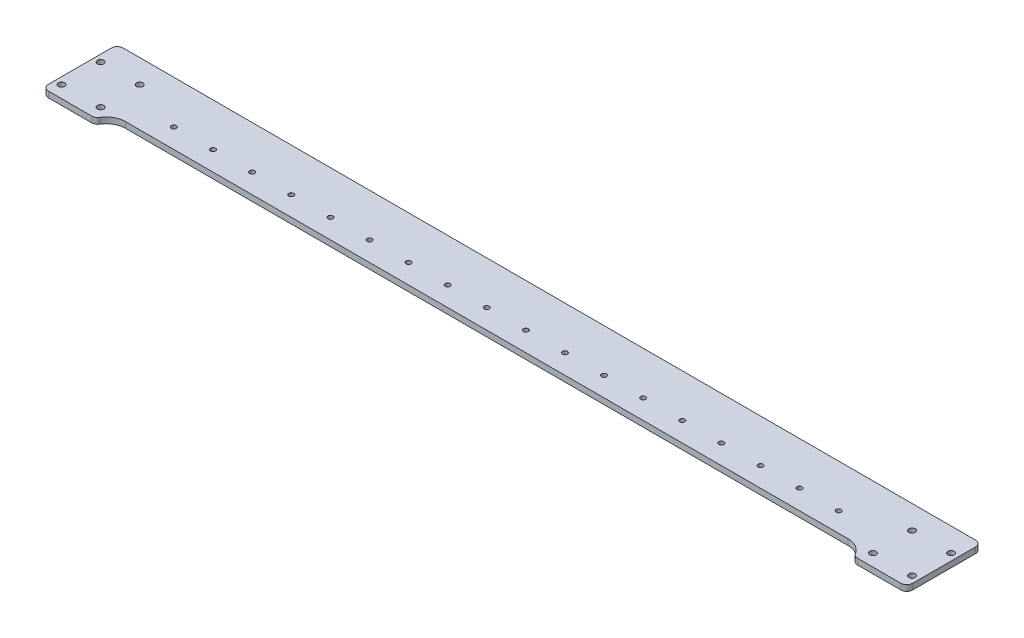
SolidWorks part; units mm, degrees
material "AISI 1045 Steel, cold drawn"
ref_plane "Front Plane" through (0, 0, 0) normal (0, 0, 1) x (1, 0, 0)
ref_plane "Top Plane" through (0, 0, 0) normal (0, 1, 0) x (1, 0, 0)
ref_plane "Right Plane" through (0, 0, 0) normal (1, 0, 0) x (0, 0, -1)
sketch "Sketch1" plane through (0, 0, 0) normal (0, 1, 0) x (1, 0, 0)
  line L0 (0, 0) -> (194, 0)
  line L1 (194, 0) -> (194, -6.2)
  line L2 (194, -6.2) -> (221, -6.2)
  line L3 (221, -6.2) -> (221, 26.2)
  line L4 (221, 26.2) -> (0, 26.2) construction
  line L7 (0, 0) -> (0, 26.2)
  line L8 (221, 10) -> (0, 10) construction
  line L9 (221, 26.2) -> (221, 32)
  line L10 (221, 32) -> (0, 32)
  line L11 (0, 32) -> (0, 26.2)
  dimension "D1" = 194
  dimension "D2" = 27
  dimension "D3" = 10
  dimension "D4" = 32.4
  dimension "D5" = 22
extrude "Boss-Extrude1" add sketch "Sketch1" along normal blind 3
hole_wizard "M3 Clearance Hole1" positions "Sketch2" profile "Sketch3" hole size "M3" standard "ANSI Metric" end condition through all
sketch "Sketch2" plane through (0, 3, 0) normal (0, 1, 0) x (1, 0, 0)
  line L1 (217.5, 0) -> (197.5, 0)
  line L2 (217.5, 0) -> (217.5, 20)
  line L3 (217.5, 20) -> (197.5, 20)
  line L4 (197.5, 0) -> (197.5, 20)
  line L5 (217.5, 0) -> (197.5, 20) construction
  line L6 (217.5, 20) -> (197.5, 0) construction
  line L10 (207.5, 10) -> (207.5, -6.2) construction
  line L13 (194, -6.2) -> (221, -6.2) construction
  line L17 (0, 0) -> (194, 0) construction
  point P2 (197.5, 20)
  point P35 (217.5, 0)
  point P36 (217.5, 20)
  point P37 (197.5, 0)
  dimension "D1" = 20
  dimension "D2" = 10
sketch "Sketch3" plane through (197.5, 3, -20) normal (1, 0, 0) x (0, 0, 1)
  line L0 (0, 0) -> (0, 3)
  line L1 (0, 3) -> (1.6, 3)
  line L2 (1.6, 3) -> (1.6, 0.025)
  line L3 (1.6, 0.025) -> (1.625, 0)
  line L5 (1.625, 0) -> (0, 0)
  line L6 (-1.6, 0.025) -> (-1.625, 0) construction
  line L11 (0, -6.35) -> (0, 107.95) construction
  dimension "Thru Hole Dia." = 3.2
  dimension "Thru Hole Depth" = 3
  dimension "Near C'Sink Dia." = 3.25
  dimension "Near C'Sink Angle" = 90
fillet "Fillet1" radius 10 1 edges at (194, 1.5, 0)
fillet "Fillet2" radius 3 3 edges at (221, 1.5, 6.2) (194, 1.5, 6.2) (221, 1.5, -32)
mirror "Mirror1" about plane through (0, 3, -32) normal (1, 0, 0) of bodies 103
sketch "Sketch4" plane through (0, 3, 0) normal (0, 1, 0) x (1, 0, 0)
  line L0 (-180, 10) -> (180, 10) construction
  line L2 (-184.7501, 0) -> (184.7501, 0) construction
  point P5 (0, 10)
  point P7 (-170, 10)
  point P8 (-150, 10)
  point P10 (-130, 10)
  point P11 (-110, 10)
  point P12 (-90, 10)
  point P13 (-70, 10)
  point P14 (-50, 10)
  point P15 (-30, 10)
  point P16 (-10, 10)
  point P17 (10, 10)
  point P18 (30, 10)
  point P19 (50, 10)
  point P20 (70, 10)
  point P21 (90, 10)
  point P22 (110, 10)
  point P23 (130, 10)
  point P24 (150, 10)
  point P25 (170, 10)
  dimension "D1" = 360
  dimension "D2" = 10
  dimension "D4" = 20
  dimension "D5" = 10
  dimension "D3" = 18
hole_wizard "Tap Drill for M3x0.5 Tap1" positions "Sketch5" profile "Sketch6" hole size "M3x0.5" standard "ANSI Metric" end condition through all
sketch "Sketch5" plane through (0, 3, 0) normal (0, 1, 0) x (1, 0, 0)
  point P0 (-170, 10)
  point P3 (-150, 10)
  point P6 (-130, 10)
  point P9 (-110, 10)
  point P12 (-90, 10)
  point P15 (-70, 10)
  point P18 (-50, 10)
  point P21 (-30, 10)
  point P24 (-10, 10)
  point P27 (10, 10)
  point P30 (30, 10)
  point P33 (50, 10)
  point P36 (70, 10)
  point P39 (170, 10)
  point P42 (150, 10)
  point P45 (130, 10)
  point P48 (110, 10)
  point P51 (90, 10)
sketch "Sketch6" plane through (-170, 3, -10) normal (1, 0, 0) x (0, 0, 1)
  line L0 (0, 0) -> (0, 3)
  line L1 (0, 3) -> (1.25, 3)
  line L2 (1.25, 3) -> (1.25, 0.025)
  line L3 (1.25, 0.025) -> (1.275, 0)
  line L5 (1.275, 0) -> (0, 0)
  line L6 (-1.25, 0.025) -> (-1.275, 0) construction
  line L11 (0, -6.35) -> (0, 107.95) construction
  dimension "Thru Hole Dia." = 2.5
  dimension "Thru Hole Depth" = 3
  dimension "Near C'Sink Dia." = 2.55
  dimension "Near C'Sink Angle" = 90
